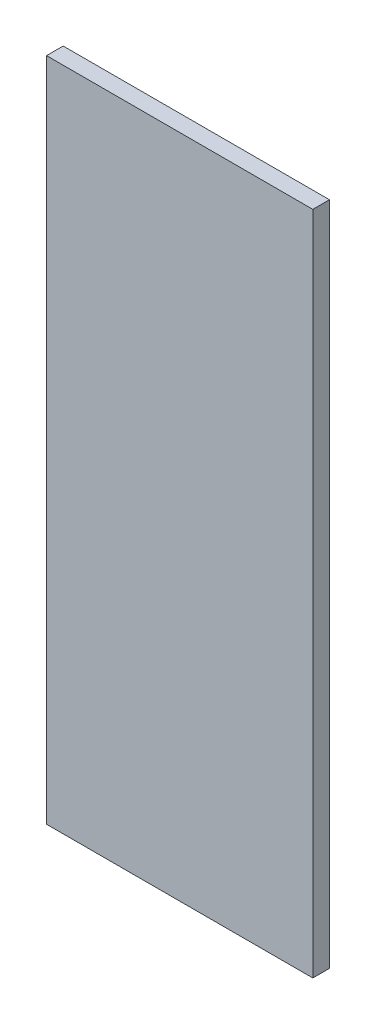
SolidWorks part; units mm, degrees
ref_plane "Front Plane" through (0, 0, 0) normal (0, 0, 1) x (1, 0, 0)
ref_plane "Top Plane" through (0, 0, 0) normal (0, 1, 0) x (1, 0, 0)
ref_plane "Right Plane" through (0, 0, 0) normal (1, 0, 0) x (0, 0, -1)
sketch "Sketch1" plane through (0, 0, 0) normal (0, 0, 1) x (1, 0, 0)
  line L1 (0, 0) -> (101.6, 0)
  line L2 (0, 0) -> (0, 254)
  line L3 (0, 254) -> (101.6, 254)
  line L4 (101.6, 0) -> (101.6, 254)
  dimension "D1" = 101.6
  dimension "D2" = 254
extrude "Boss-Extrude1" add sketch "Sketch1" along normal blind 6.35
